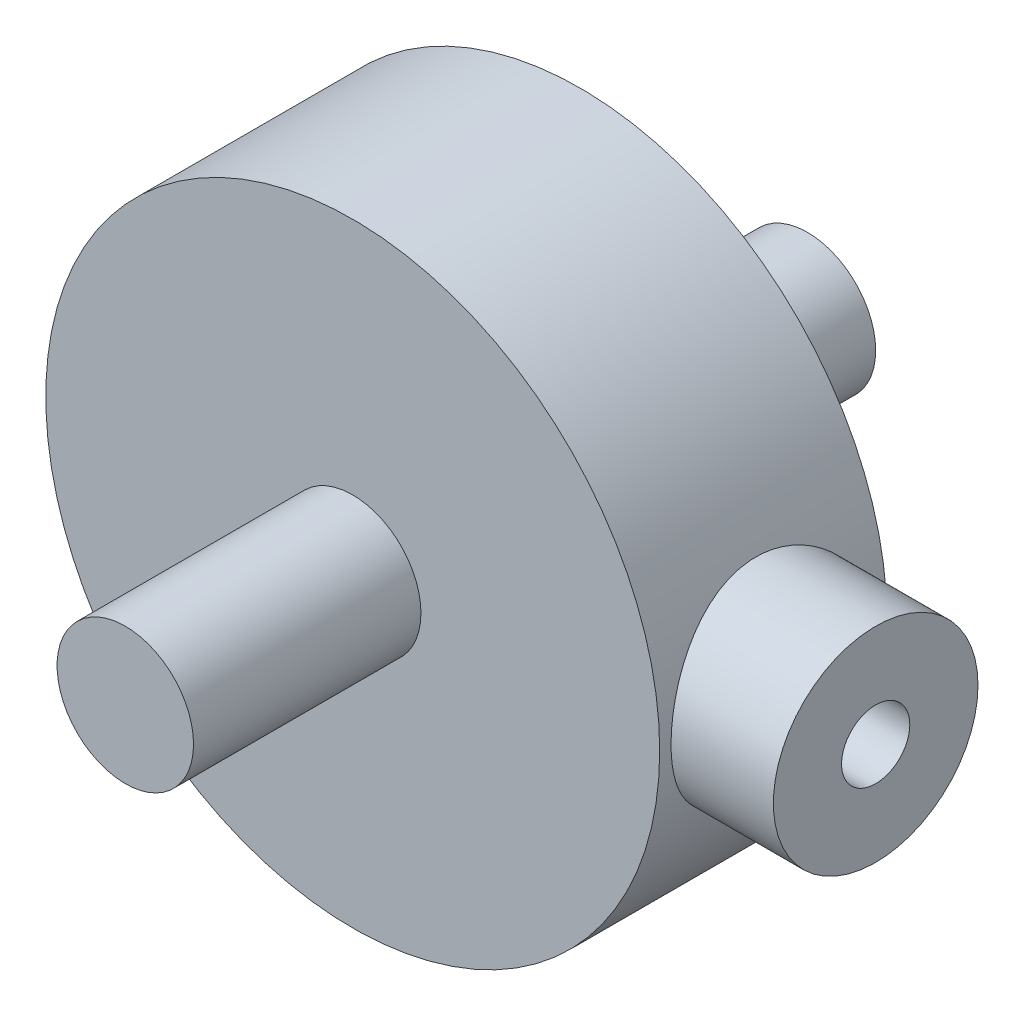
SolidWorks part; units mm, degrees
ref_plane "Front Plane" through (0, 0, 0) normal (0, 0, 1) x (1, 0, 0)
ref_plane "Top Plane" through (0, 0, 0) normal (0, 1, 0) x (1, 0, 0)
ref_plane "Right Plane" through (0, 0, 0) normal (1, 0, 0) x (0, 0, -1)
sketch "Sketch1" plane through (0, 0, 0) normal (0, 0, 1) x (1, 0, 0)
  circle A0 centre (0, 0) radius 22.5
  dimension "D1" = 45
extrude "Boss-Extrude1" add sketch "Sketch1" along normal blind 8.33 and the other way blind 8.33
sketch "Sketch2" plane through (0, 0, 0) normal (1, 0, 0) x (0, 0, -1)
  circle A0 centre (0, 0) radius 7.5
  dimension "D1" = 15
extrude "Boss-Extrude2" add sketch "Sketch2" along normal blind 20 from offset 10
sketch "Sketch3" plane through (30, 0, 0) normal (1, 0, 0) x (0, 0, -1)
  circle A0 centre (0, 0) radius 2.5
  dimension "D1" = 5
extrude "Cut-Extrude2" cut sketch "Sketch3" against normal blind 10
sketch "Sketch4" plane through (0, 0, 0) normal (0, 1, 0) x (1, 0, 0)
  line L1 (0, 0) -> (-150, 0) construction
  text T1 "Y4\r\n\r\n" font "Century Gothic" height 20
  dimension "D1" = 150
sketch "Sketch5" plane through (0, 0, 0) normal (1, 0, 0) x (0, 0, -1)
  line L0 (0, 0) -> (0, 150) construction
  text T0 "X4\r\n" font "Century Gothic" height 20
  dimension "D1" = 150
sketch "Sketch6" plane through (0, 0, 0) normal (0, 1, 0) x (1, 0, 0)
  line L0 (0, 0) -> (0, -150) construction
  text T0 "Z4" font "Century Gothic" height 16
  dimension "D1" = 150
sketch "Sketch7" plane through (0, 0, 0) normal (0, 0, 1) x (1, 0, 0)
  circle A0 centre (0, 0) radius 5
  dimension "D1" = 10
extrude "Boss-Extrude3" add sketch "Sketch7" along normal blind 25 and the other way blind 25
